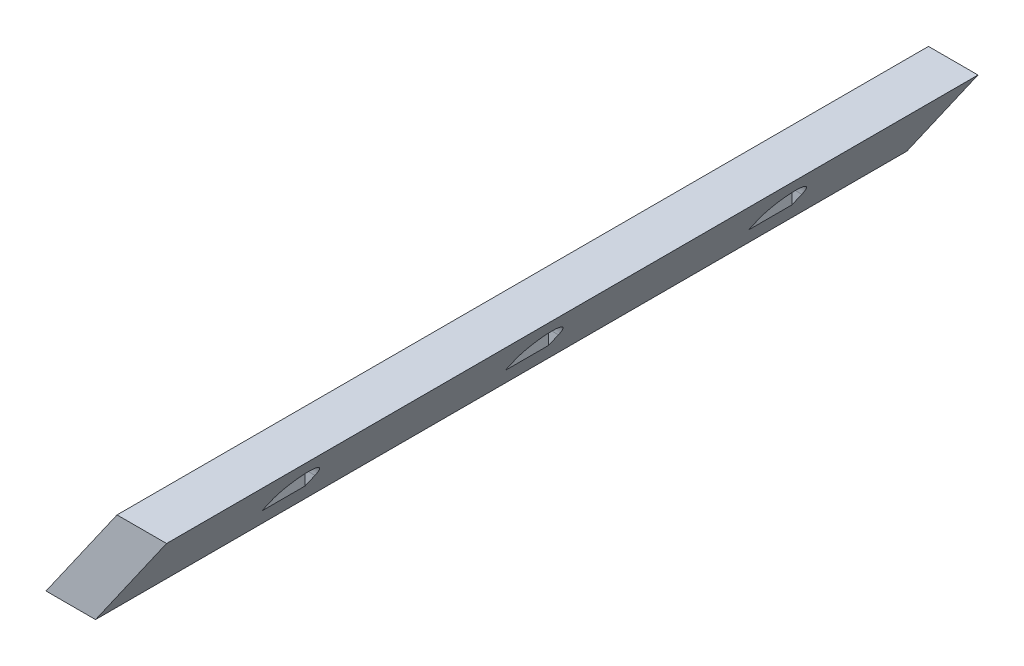
SolidWorks part; units mm, degrees
material "Gray Cast Iron"
ref_plane "Front Plane" through (0, 0, 0) normal (0, 0, 1) x (1, 0, 0)
ref_plane "Top Plane" through (0, 0, 0) normal (0, 1, 0) x (1, 0, 0)
ref_plane "Right Plane" through (0, 0, 0) normal (1, 0, 0) x (0, 0, -1)
sketch "end-profile" plane through (0, 0, 0) normal (0, 0, 1) x (1, 0, 0)
  line L0 (0, 0) -> (7.7519, 0)
  line L1 (7.7519, 0) -> (18.8677, 15.875)
  line L2 (18.8677, 15.875) -> (11.1158, 15.875)
  line L3 (11.1158, 15.875) -> (0, 0)
  dimension "D1" = 55
  dimension "D2" = 6.35
  dimension "D3" = 15.875
extrude "Boss-Extrude1" add sketch "end-profile" along normal blind 127
ref_plane "screw pocket Plane1" through (18.8677, 0, 0) normal (1, 0, 0) x (0, 0, -1)
sketch "Sketch4" [suppressed] plane through (18.8677, 0, 0) normal (1, 0, 0) x (0, 0, -1)
  line L0 (0, 7.9375) -> (-203.2, 7.9375) construction
  line L1 (0, 0) -> (0, 15.875) construction
  line L2 (-203.2, 0) -> (-203.2, 15.875) construction
  line L3 (-181.1871, 7.9375) -> (-181.1871, 0)
  line L4 (-181.1871, 0) -> (-174.4129, 0)
  line L5 (-174.4129, 0) -> (-174.4129, 7.9375)
  line L6 (-143.0871, 7.9375) -> (-143.0871, 0)
  line L7 (-143.0871, 0) -> (-136.3129, 0)
  line L8 (-136.3129, 0) -> (-136.3129, 7.9375)
  line L9 (-104.9871, 7.9375) -> (-104.9871, 0)
  line L10 (-104.9871, 0) -> (-98.2129, 0)
  line L11 (-98.2129, 0) -> (-98.2129, 7.9375)
  line L12 (-66.8871, 7.9375) -> (-66.8871, 0)
  line L13 (-66.8871, 0) -> (-60.1129, 0)
  line L14 (-60.1129, 0) -> (-60.1129, 7.9375)
  line L15 (-28.7871, 7.9375) -> (-28.7871, 0)
  line L16 (-28.7871, 0) -> (-22.0129, 0)
  line L17 (-22.0129, 0) -> (-22.0129, 7.9375)
  line L18 (-181.1871, 7.9375) -> (-143.0871, 7.9375) construction
  line L20 (-203.2, 0) -> (0, 0) construction
  arc A0 (-174.4129, 7.9375) -> (-181.1871, 7.9375) centre (-177.8, 7.9375) ccw
  arc A1 (-136.3129, 7.9375) -> (-143.0871, 7.9375) centre (-139.7, 7.9375) ccw
  arc A2 (-98.2129, 7.9375) -> (-104.9871, 7.9375) centre (-101.6, 7.9375) ccw
  arc A3 (-60.1129, 7.9375) -> (-66.8871, 7.9375) centre (-63.5, 7.9375) ccw
  arc A4 (-22.0129, 7.9375) -> (-28.7871, 7.9375) centre (-25.4, 7.9375) ccw
  dimension "D1" = 6.7742
  dimension "D2" = 38.1
  dimension "D3" = 5
extrude "Cut-Extrude1" [suppressed] cut sketch "Sketch4" against normal blind 7.112
sketch "Sketch5" plane through (18.8677, 0, 0) normal (1, 0, 0) x (0, 0, -1)
  line L0 (0, 7.9375) -> (-127, 7.9375) construction
  line L1 (0, 0) -> (0, 15.875) construction
  line L2 (-127, 0) -> (-127, 15.875) construction
  line L3 (-104.9871, 7.9375) -> (-104.9871, 0)
  line L4 (-127, 0) -> (0, 0) construction
  line L5 (-104.9871, 0) -> (-98.2129, 0)
  line L6 (-98.2129, 0) -> (-98.2129, 7.9375)
  line L7 (-66.8871, 7.9375) -> (-66.8871, 0)
  line L8 (-66.8871, 0) -> (-60.1129, 0)
  line L9 (-60.1129, 0) -> (-60.1129, 7.9375)
  line L10 (-28.7871, 7.9375) -> (-28.7871, 0)
  line L11 (-28.7871, 0) -> (-22.0129, 0)
  line L12 (-22.0129, 0) -> (-22.0129, 7.9375)
  line L13 (-104.9871, 7.9375) -> (-66.8871, 7.9375) construction
  arc A0 (-98.2129, 7.9375) -> (-104.9871, 7.9375) centre (-101.6, 7.9375) ccw
  arc A1 (-60.1129, 7.9375) -> (-66.8871, 7.9375) centre (-63.5, 7.9375) ccw
  arc A2 (-22.0129, 7.9375) -> (-28.7871, 7.9375) centre (-25.4, 7.9375) ccw
  dimension "D1" = 6.7742
  dimension "D2" = 38.1
extrude "Cut-Extrude2" cut sketch "Sketch5" against normal blind 7.112
equation "\"dovetail-angle\"= 55"
equation "\"dovetail-stock-width\"= 5"
equation "\"dovetail-stock-height\"= 1.25"
equation "\"dovetail-depth\"= 0.5 * \"dovetail-stock-height\""
equation "\"dovetail-throat-width\"= \"dovetail-stock-width\" - (2 * \"dovetail-depth\")"
equation "\"delta-x\"= 6"
equation "\"delta-y\"= 3"
equation "\"delta-z\"= 2.5"
equation "\"acme-nut-height\"= 0.5"
equation "\"acme-nut-width\"= 0.75"
equation "\"gib-thickness\"= 0.25"
equation "\"x-slide-length\"= \"dovetail-stock-width\" + \"delta-x\""
equation "\"y-slide-length\"= \"dovetail-stock-width\" + \"delta-y\""
equation "\"dog-point-diam\"= .149"
equation "\"dog-point-length\"= .067"
equation "\"dovetail-double-height\"= 2 * \"dovetail-depth\" + 0.5"
equation "\"D1@end-profile\"=\"dovetail-angle\""
equation "\"D2@end-profile\"=\"gib-thickness\""
equation "\"D1@Boss-Extrude1\"     = \"dovetail-stock-width\""
equation "\"acme-major-diam\"= .5"
equation "\"acme-pitch-diam\"= 0.45"
equation "\"acme-minor-diam\"= 0.4"
equation "\"acme-nut-od\"= 1.47"
equation "\"acme-nut-length\"= 1"
equation "\"acme-nut-trim-height\"= .75"
equation "\"screw-bearing-od\"= 0.5"
equation "\"screw-bearing-length\"= .25"
equation "\"screw-bearing-id\"= .375"
equation "\"end-plate-thickness\"= \"screw-bearing-length\""
equation "\"screw-add-length\"= 2 * \"end-plate-thickness\" + 1 + 0.5"
equation "\"x-screw-length\"= \"x-slide-length\" + \"screw-add-length\""
equation "\"y-screw-length\"= \"y-slide-length\" + \"screw-add-length\""
equation "\"acme-nut-mount-hole-space-horz\"= 0.82"
equation "\"acme-nut-mount-hole-space-vert\"= 0.5 * \"acme-nut-length\""
equation "\"D3@end-profile\"=\"dovetail-depth\""
equation "\"vise-hole-center-dist\"= 6.75"
equation "\"wiper_plate_clearance\"= .03"
equation "\"dial-width\"= 0.5"
equation "\"quarter-twenty-free-fit\"= .2667"
equation "\"D1@Sketch4\"=\"quarter-twenty-free-fit\""
equation "\"D1@Sketch5\"=\"quarter-twenty-free-fit\""
